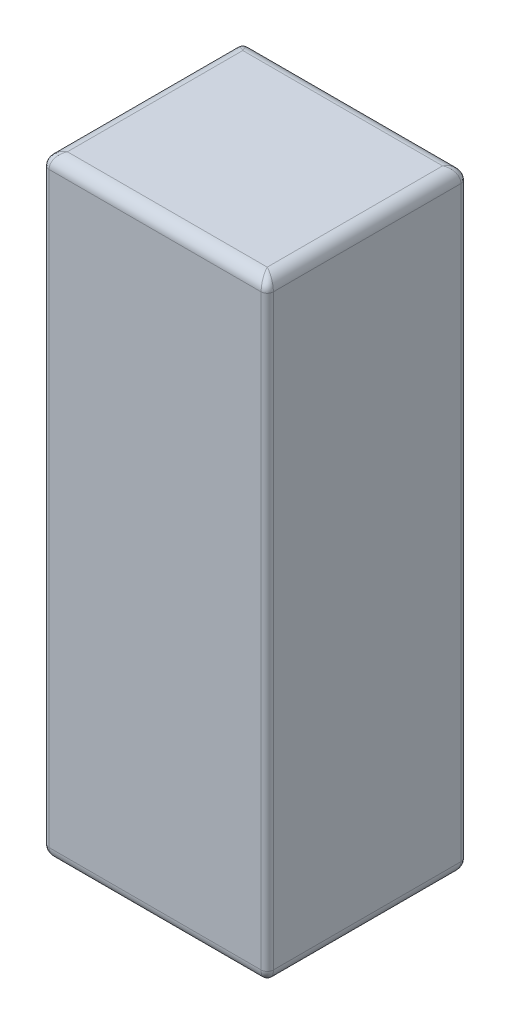
SolidWorks part; units mm, degrees
ref_plane "Front Plane" through (0, 0, 0) normal (0, 0, 1) x (1, 0, 0)
ref_plane "Top Plane" through (0, 0, 0) normal (0, 1, 0) x (1, 0, 0)
ref_plane "Right Plane" through (0, 0, 0) normal (1, 0, 0) x (0, 0, -1)
sketch "Sketch1" plane through (0, 0, 0) normal (0, 1, 0) x (1, 0, 0)
  line L1 (-27.348, 24.5043) -> (27.652, 24.5043)
  line L2 (-27.348, 24.5043) -> (-27.348, -24.4957)
  line L3 (-27.348, -24.4957) -> (27.652, -24.4957)
  line L4 (27.652, 24.5043) -> (27.652, -24.4957)
  line L5 (-27.348, 24.5043) -> (27.652, -24.4957) construction
  line L6 (-27.348, -24.4957) -> (27.652, 24.5043) construction
  point P0 (0.152, 0.0043)
extrude "Boss-Extrude1" add sketch "Sketch1" along normal blind 150
fillet "Fillet1" radius 1.5 4 edges at (-27.348, 75, -24.5043) (27.652, 75, -24.5043) (27.652, 75, 24.4957) (-27.348, 75, 24.4957)
fillet "Fillet2" radius 3 16 edges at (27.2127, 0, -24.0649) (27.652, 0, -0.0043) (27.2127, 0, 24.0564) (0.152, 0, 24.4957) (-26.9086, 0, 24.0564) (-27.348, 0, -0.0043) (-26.9086, 0, -24.0649) (27.2127, 150, 24.0564) (0.152, 150, 24.4957) (-26.9086, 150, 24.0564) (-27.348, 150, -0.0043) (-26.9086, 150, -24.0649) (0.152, 150, -24.5043) (27.2127, 150, -24.0649) (0.152, 0, -24.5043) (27.652, 150, -0.0043)
